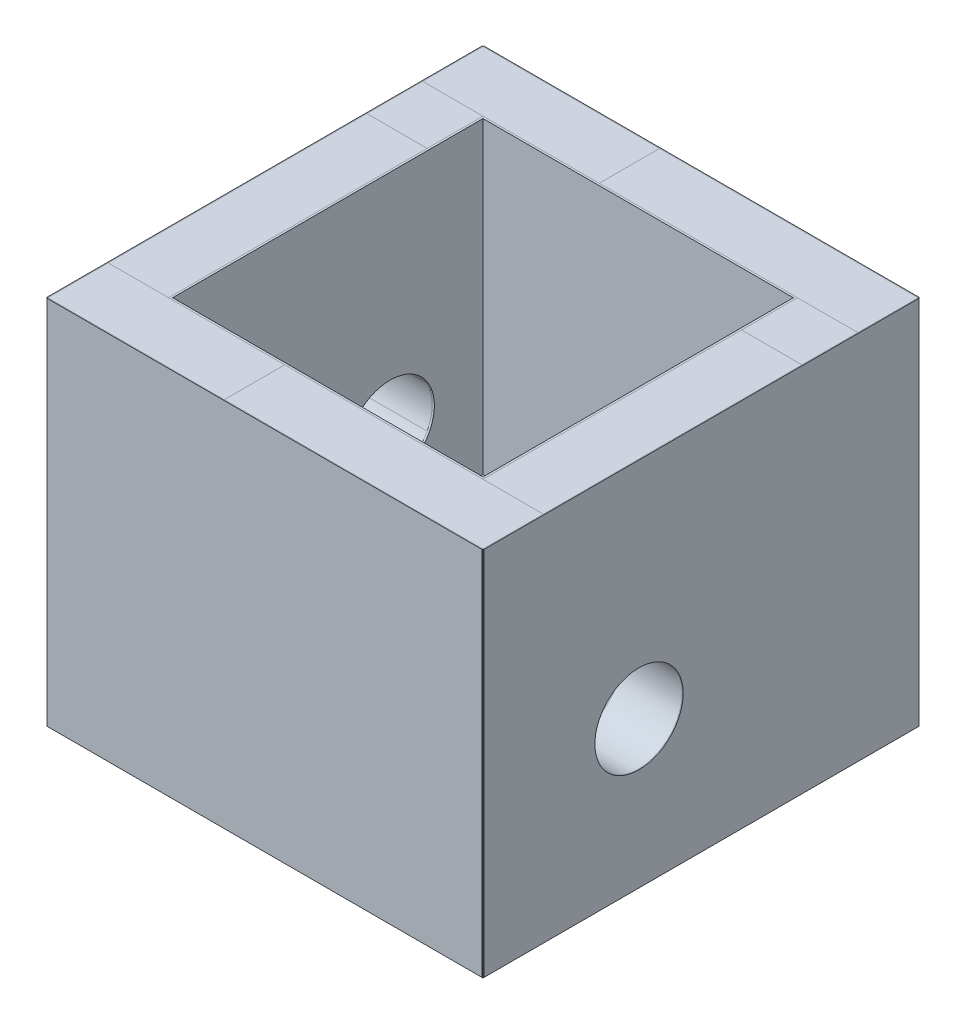
SolidWorks part; units mm, degrees
ref_plane "Front Plane" through (0, 0, 0) normal (0, 0, 1) x (1, 0, 0)
ref_plane "Top Plane" through (0, 0, 0) normal (0, 1, 0) x (1, 0, 0)
ref_plane "Right Plane" through (0, 0, 0) normal (1, 0, 0) x (0, 0, -1)
sketch "Sketch1" plane through (0, 0, 0) normal (0, 1, 0) x (1, 0, 0)
  line L1 (0, 0) -> (457.2, 0)
  line L2 (0, 0) -> (0, 457.2)
  line L3 (0, 457.2) -> (457.2, 457.2)
  line L4 (457.2, 0) -> (457.2, 457.2)
  dimension "D1" = 457.2
  dimension "D2" = 457.2
extrude "Boss-Extrude1" add sketch "Sketch1" along normal blind 3.048
sketch "Sketch2" plane through (0, 0, 0) normal (-1, 0, 0) x (0, 0, 1)
  line L1 (-457.2, 0) -> (0, 0)
  line L2 (-457.2, 0) -> (-457.2, 457.2)
  line L3 (-457.2, 457.2) -> (0, 457.2)
  line L4 (0, 0) -> (0, 457.2)
  dimension "D1" = 457.2
extrude "Boss-Extrude2" add sketch "Sketch2" along normal blind 3.048
sketch "Sketch3" plane through (0, 0, 0) normal (0, 0, 1) x (1, 0, 0)
  line L0 (457.2, 3.048) -> (457.2, 0) construction
  line L1 (-3.048, 0) -> (457.2, 0)
  line L2 (-3.048, 0) -> (-3.048, 457.2)
  line L3 (-3.048, 457.2) -> (457.2, 457.2)
  line L4 (457.2, 0) -> (457.2, 457.2)
  line L5 (-3.048, 457.2) -> (0, 457.2) construction
extrude "Boss-Extrude3" add sketch "Sketch3" along normal blind 3.048
sketch "Sketch4" plane through (457.2, 0, 0) normal (1, 0, 0) x (0, 0, -1)
  line L0 (457.2, 457.2) -> (457.2, 3.048) construction
  line L1 (-3.048, 0) -> (457.2, 0)
  line L2 (-3.048, 0) -> (-3.048, 457.2)
  line L3 (-3.048, 457.2) -> (457.2, 457.2)
  line L4 (457.2, 0) -> (457.2, 457.2)
  line L6 (-3.048, 0) -> (457.2, 0)
  line L7 (457.2, 0) -> (457.2, 3.048)
  line L8 (457.2, 3.048) -> (0, 3.048)
  line L9 (0, 3.048) -> (0, 457.2)
  line L10 (0, 457.2) -> (-3.048, 457.2)
  line L11 (-3.048, 457.2) -> (-3.048, 0)
  line L12 (-3.048, 0) -> (457.2, 0)
  line L13 (457.2, 0) -> (457.2, 3.048)
  line L14 (457.2, 3.048) -> (0, 3.048)
  line L15 (0, 3.048) -> (0, 457.2)
  line L16 (0, 457.2) -> (-3.048, 457.2)
  line L17 (-3.048, 457.2) -> (-3.048, 0)
  line M7 (-3.048, 0) -> (457.2, 0)
  line M8 (457.2, 0) -> (457.2, 3.048)
  line M9 (457.2, 3.048) -> (0, 3.048)
  line M10 (0, 3.048) -> (0, 457.2)
  line M11 (0, 457.2) -> (-3.048, 457.2)
  line M12 (-3.048, 457.2) -> (-3.048, 0)
  dimension "D1" = 0
extrude "Boss-Extrude4" add sketch "Sketch4" along normal blind 3.048 contours M12 M7 M8 M9 M10 M11 | L4 L3 M9 M10 region at (457.2, 228.6, 2.3993) region at (457.2, 230.124, -228.6)
sketch "Sketch5" plane through (0, 0, -457.2) normal (0, 0, -1) x (-1, 0, 0)
  line L1 (-460.248, 0) -> (3.048, 0)
  line L2 (-460.248, 0) -> (-460.248, 457.2)
  line L3 (-460.248, 457.2) -> (3.048, 457.2)
  line L4 (3.048, 0) -> (3.048, 457.2)
  line L8 (-460.248, 0) -> (3.048, 0)
  line L9 (3.048, 0) -> (3.048, 457.2)
  line L10 (3.048, 457.2) -> (0, 457.2)
  line L11 (0, 457.2) -> (0, 3.048)
  line L12 (0, 3.048) -> (-457.2, 3.048)
  line L13 (-457.2, 3.048) -> (-457.2, 457.2)
  line L14 (-457.2, 457.2) -> (-460.248, 457.2)
  line L15 (-460.248, 457.2) -> (-460.248, 0)
  line L16 (-460.248, 0) -> (3.048, 0)
  line L17 (3.048, 0) -> (3.048, 457.2)
  line L18 (3.048, 457.2) -> (0, 457.2)
  line L19 (0, 457.2) -> (0, 3.048)
  line L20 (0, 3.048) -> (-457.2, 3.048)
  line L21 (-457.2, 3.048) -> (-457.2, 457.2)
  line L23 (-460.248, 457.2) -> (-460.248, 0)
  line L28 (-457.2, 457.2) -> (-460.248, 457.2)
  line M9 (-460.248, 0) -> (3.048, 0)
  line M10 (3.048, 0) -> (3.048, 457.2)
  line M11 (3.048, 457.2) -> (0, 457.2)
  line M12 (0, 457.2) -> (0, 3.048)
  line M13 (0, 3.048) -> (-457.2, 3.048)
  line M14 (-457.2, 3.048) -> (-457.2, 457.2)
  line M15 (-457.2, 457.2) -> (-460.248, 457.2)
  line M16 (-460.248, 457.2) -> (-460.248, 0)
  dimension "D1" = 0
extrude "Boss-Extrude5" add sketch "Sketch5" along normal blind 3.048 contours L3 M14 M13 M12 | M16 M9 M10 M11 M12 M13 M14 M15 region at (459.5971, 228.6, -457.2) region at (228.6, 230.124, -457.2)
ref_plane "Plane1" through (228.6, 0, 0) normal (1, 0, 0) x (0, 0, -1)
sketch "Sketch6" plane through (460.248, 0, 0) normal (1, 0, 0) x (0, 0, -1)
  line L1 (-3.048, 457.2) -> (377.952, 457.2)
  line L2 (-3.048, 457.2) -> (-3.048, 0)
  line L3 (-3.048, 0) -> (377.952, 0)
  line L4 (-3.048, 457.2) -> (-3.048, 0)
  line L5 (-3.048, 0) -> (460.248, 0)
  line L6 (460.248, 0) -> (460.248, 457.2)
  line L7 (460.248, 457.2) -> (-3.048, 457.2)
  line L8 (-3.048, 457.2) -> (-3.048, 0)
  line L9 (-3.048, 0) -> (460.248, 0)
  line L10 (460.248, 0) -> (460.248, 457.2)
  line L11 (460.248, 457.2) -> (-3.048, 457.2)
  line L12 (377.952, 457.2) -> (377.952, 0)
  line L13 (460.248, 0) -> (377.952, 0)
  line L14 (460.248, 0) -> (460.248, 381)
  line L15 (460.248, 381) -> (377.952, 381)
  line L16 (377.952, 0) -> (377.952, 381)
  line L17 (377.952, 381) -> (460.248, 381)
  line L18 (377.952, 381) -> (377.952, 457.2)
  line L19 (377.952, 457.2) -> (460.248, 457.2)
  line L20 (460.248, 381) -> (460.248, 457.2)
  line M10 (-3.048, 457.2) -> (-3.048, 0)
  line M11 (-3.048, 0) -> (460.248, 0)
  line M12 (460.248, 0) -> (460.248, 457.2)
  line M13 (460.248, 457.2) -> (-3.048, 457.2)
  dimension "D2" = 381
  dimension "D3" = 381
  dimension "D1" = 0
extrude "Boss-Extrude6" add sketch "Sketch6" along normal blind 88.9 separate body contours L12 M13 M10 M11 region at (460.248, 228.6, -187.452)
extrude "Boss-Extrude7" add sketch "Sketch6<3>" along normal blind 88.9 separate body contours L15 L10 L12 M13 region at (460.248, 419.1, -419.1)
sketch "Sketch6<3>" plane through (460.248, 0, 0) normal (1, 0, 0) x (0, 0, -1) same geometry as "Sketch6"
extrude "Boss-Extrude8" add sketch "Sketch6<4>" along normal blind 88.9 separate body contours L15 L12 M12 M11 region at (460.248, 190.5, -419.1)
sketch "Sketch6<4>" plane through (460.248, 0, 0) normal (1, 0, 0) x (0, 0, -1) same geometry as "Sketch6"
mirror "Mirror1" about plane through (228.6, 0, 0) normal (1, 0, 0) of bodies 116 115 117
sketch "Sketch7" plane through (0, 0, -460.248) normal (0, 0, -1) x (-1, 0, 0)
  line L0 (-460.248, 0) -> (3.048, 0) construction
  line L1 (-549.148, 457.2) -> (-168.148, 457.2)
  line L2 (-549.148, 457.2) -> (-549.148, 0)
  line L3 (-549.148, 0) -> (-168.148, 0)
  line L4 (-168.148, 457.2) -> (-168.148, 0)
  line L5 (91.948, 381) -> (91.948, 457.2) construction
  line L6 (-168.148, 457.2) -> (91.948, 457.2)
  line L7 (-168.148, 457.2) -> (-168.148, 76.2)
  line L8 (-168.148, 76.2) -> (91.948, 76.2)
  line L9 (91.948, 457.2) -> (91.948, 76.2)
  line L11 (-168.148, 76.2) -> (91.948, 76.2)
  line L12 (-168.148, 76.2) -> (-168.148, 0)
  line L13 (-168.148, 0) -> (91.948, 0)
  line L14 (91.948, 76.2) -> (91.948, 0)
  line M9 (-460.248, 0) -> (-460.248, 381)
  line M10 (-460.248, 381) -> (-549.148, 381)
  line M11 (-549.148, 381) -> (-549.148, 0)
  line M12 (-549.148, 0) -> (-460.248, 0)
  dimension "D1" = 381
  dimension "D3" = 381
extrude "Boss-Extrude9" add sketch "Sketch7" along normal blind 88.9 separate body contours L4 L1 L2 L3 M10 M9 | M12 M9 M10 M11 region at (323.3946, 237.7966, -460.248) region at (504.698, 190.5, -460.248)
extrude "Boss-Extrude10" add sketch "Sketch7<3>" along normal blind 88.9 separate body contours L9 L6 L4 L8 region at (38.1, 266.7, -460.248)
sketch "Sketch7<3>" plane through (0, 0, -460.248) normal (0, 0, -1) x (-1, 0, 0) same geometry as "Sketch7"
extrude "Boss-Extrude11" add sketch "Sketch7<4>" along normal blind 88.9 separate body contours L14 L8 L4 L13 region at (38.1, 38.1, -460.248)
sketch "Sketch7<4>" plane through (0, 0, -460.248) normal (0, 0, -1) x (-1, 0, 0) same geometry as "Sketch7"
ref_plane "Plane2" through (0, 0, -228.6) normal (0, 0, -1) x (-1, 0, 0)
mirror "Mirror2" about plane through (0, 0, -228.6) normal (0, 0, -1) of bodies 122 121 123
sketch "Sketch8" plane through (0, 0, 0) normal (0, -1, 0) x (1, 0, 0)
  line L0 (549.148, -549.148) -> (168.148, -549.148) construction
  line L1 (-91.948, 91.948) -> (289.052, 91.948)
  line L2 (-91.948, 91.948) -> (-91.948, -549.148)
  line L3 (-91.948, -549.148) -> (289.052, -549.148)
  line L4 (289.052, 91.948) -> (289.052, -549.148)
  line L5 (549.148, 3.048) -> (549.148, -377.952) construction
  line L6 (289.052, 91.948) -> (549.148, 91.948)
  line L7 (289.052, 91.948) -> (289.052, -289.052)
  line L8 (289.052, -289.052) -> (549.148, -289.052)
  line L9 (549.148, 91.948) -> (549.148, -289.052)
  line L11 (289.052, -289.052) -> (549.148, -289.052)
  line L12 (289.052, -289.052) -> (289.052, -549.148)
  line L13 (289.052, -549.148) -> (549.148, -549.148)
  line L14 (549.148, -289.052) -> (549.148, -549.148)
  line M7 (-3.048, 3.048) -> (-3.048, -460.248)
  line M8 (-3.048, -460.248) -> (460.248, -460.248)
  line M9 (460.248, -460.248) -> (460.248, 3.048)
  line M10 (460.248, 3.048) -> (-3.048, 3.048)
  dimension "D1" = 381
  dimension "D2" = 381
extrude "Boss-Extrude12" add sketch "Sketch8" along normal blind 88.9 separate body contours L4 M10 M7 M8 | L4 L1 L2 L3 M8 M7 M10 region at (98.552, 0, 84.4904) region at (143.002, 0, -228.6)
extrude "Boss-Extrude13" add sketch "Sketch8<3>" along normal blind 88.9 separate body contours L4 L8 M9 M10 | L9 L6 L4 L8 M10 M9 region at (464.3795, 0, -53.2725) region at (374.65, 0, -143.002)
sketch "Sketch8<3>" plane through (0, 0, 0) normal (0, -1, 0) x (1, 0, 0) same geometry as "Sketch8"
extrude "Boss-Extrude14" add sketch "Sketch8<4>" along normal blind 88.9 separate body contours L8 L4 M8 M9 | L14 L8 L4 L13 M9 M8 region at (374.65, 0, -374.65) region at (292.7303, 0, -504.698)
sketch "Sketch8<4>" plane through (0, 0, 0) normal (0, -1, 0) x (1, 0, 0) same geometry as "Sketch8"
sketch "Sketch9" plane through (549.148, 0, 0) normal (1, 0, 0) x (0, 0, -1)
  line L1 (-91.948, 457.2) -> (549.148, 457.2)
  line L2 (-91.948, 457.2) -> (-91.948, -88.9)
  line L3 (-91.948, -88.9) -> (549.148, -88.9)
  line L4 (549.148, 457.2) -> (549.148, -88.9)
extrude "Boss-Extrude15" add sketch "Sketch9" along normal blind 1.2192 separate body
sketch "Sketch10" plane through (0, 0, -549.148) normal (0, 0, -1) x (-1, 0, 0)
  line L1 (-549.148, 457.2) -> (91.948, 457.2)
  line L2 (-549.148, 457.2) -> (-549.148, -88.9)
  line L3 (-549.148, -88.9) -> (91.948, -88.9)
  line L4 (91.948, 457.2) -> (91.948, -88.9)
extrude "Boss-Extrude16" add sketch "Sketch10" along normal blind 1.2192 separate body
mirror "Mirror3" about plane through (228.6, 0, 0) normal (1, 0, 0) of bodies 130
mirror "Mirror4" about plane through (0, 0, -228.6) normal (0, 0, -1) of bodies 131
sketch "Sketch11" plane through (0, -88.9, 0) normal (0, -1, 0) x (1, 0, 0)
  line L1 (-91.948, 91.948) -> (549.148, 91.948)
  line L2 (-91.948, 91.948) -> (-91.948, -549.148)
  line L3 (-91.948, -549.148) -> (549.148, -549.148)
  line L4 (549.148, 91.948) -> (549.148, -549.148)
extrude "Boss-Extrude17" add sketch "Sketch11" along normal blind 1.2192 separate body
sketch "Sketch12" plane through (-93.1672, 0, 0) normal (-1, 0, 0) x (0, 0, 1)
  line L4 (91.948, -88.9) -> (91.948, 457.2)
  line L5 (91.948, 457.2) -> (-549.148, 457.2)
  line L6 (-549.148, 457.2) -> (-549.148, -88.9)
  line L7 (-549.148, -88.9) -> (91.948, -88.9)
  line L8 (91.948, -88.9) -> (91.948, 457.2)
  line L9 (91.948, 457.2) -> (-549.148, 457.2)
  line L10 (-549.148, 457.2) -> (-549.148, -88.9)
  line L11 (-549.148, -88.9) -> (91.948, -88.9)
  circle A0 centre (-320.548, 127) radius 65
  dimension "D2" = 330.2
  dimension "D3" = 130
  dimension "D4" = 228.6
  dimension "D1" = 0
extrude "Cut-Extrude1" cut sketch "Sketch12" against normal up to surface (550.3672 mm away) contours A0 region at (-93.1672, 127, -320.548) up to face at (457.2, 230.124, -228.6)
ref_axis "Axis1" through (228.6, 479.9076, -228.6) along (0, -1, 0)
sketch "Sketch14" plane through (550.3672, 0, 0) normal (1, 0, 0) x (0, 0, -1)
  line L0 (-91.948, 457.2) -> (-91.948, -88.9) construction
  line L1 (549.148, 457.2) -> (-91.948, 457.2) construction
  circle A0 centre (136.652, 127) radius 65.024
  dimension "D1" = 130.048
  dimension "D2" = 228.6
  dimension "D3" = 330.2
extrude "Cut-Extrude2" cut sketch "Sketch14" against normal up to surface (550.3672 mm away) up to face at (0, 127, -385.548)
